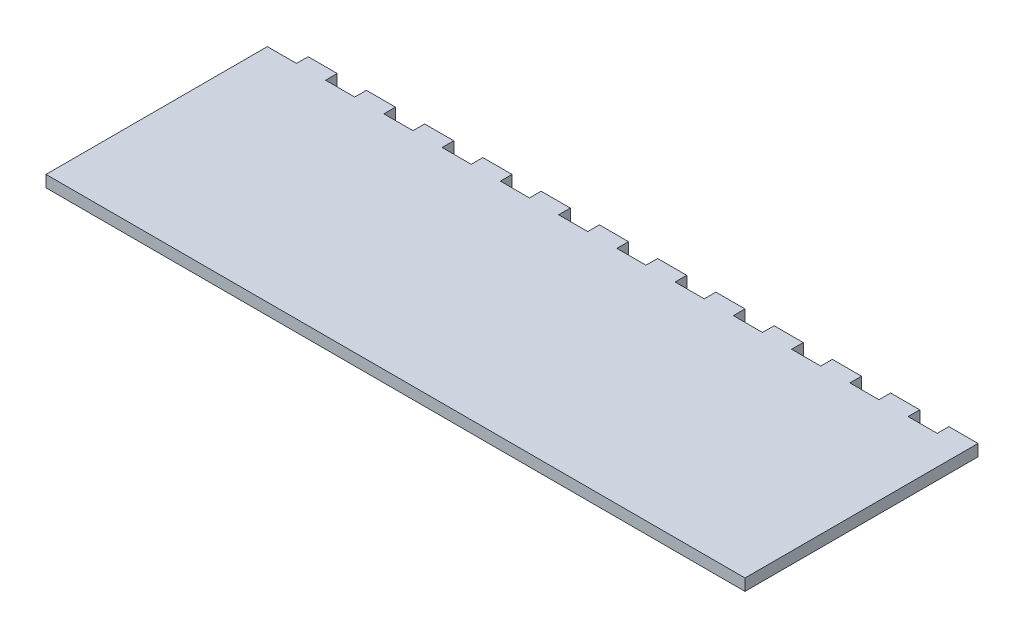
SolidWorks part; units mm, degrees
ref_plane "Front Plane" through (0, 0, 0) normal (0, 0, 1) x (1, 0, 0)
ref_plane "Top Plane" through (0, 0, 0) normal (0, 1, 0) x (1, 0, 0)
ref_plane "Right Plane" through (0, 0, 0) normal (1, 0, 0) x (0, 0, -1)
sketch "Sketch1" plane through (0, 0, 0) normal (0, 1, 0) x (1, 0, 0)
  line L1 (-76.2, -25.4) -> (76.2, -25.4)
  line L2 (-76.2, -25.4) -> (-76.2, 25.4)
  line L3 (-76.2, 25.4) -> (76.2, 25.4)
  line L4 (76.2, -25.4) -> (76.2, 25.4)
  line L5 (-76.2, -25.4) -> (76.2, 25.4) construction
  line L6 (-76.2, 25.4) -> (76.2, -25.4) construction
  point P0 (0, 0)
  dimension "D1" = 152.4
  dimension "D2" = 50.8
extrude "Boss-Extrude1" add sketch "Sketch1" along normal blind 2.54
sketch "Sketch2" plane through (0, 2.54, 0) normal (0, 1, 0) x (1, 0, 0)
  line L0 (-76.2, 22.86) -> (-69.85, 22.86)
  line L1 (-76.2, 25.4) -> (-76.2, -25.4) construction
  line L2 (-69.85, 22.86) -> (-69.85, 25.4)
  line L3 (76.2, 25.4) -> (-76.2, 25.4) construction
  line L4 (-69.85, 25.4) -> (-63.5, 25.4)
  line L5 (-76.2, 22.86) -> (-76.2, 25.4)
  line L6 (-63.5, 22.86) -> (-63.5, 25.4)
  line L7 (-63.5, 22.86) -> (-57.15, 22.86)
  line L8 (-57.15, 22.86) -> (-57.15, 25.4)
  line L9 (-57.15, 25.4) -> (-50.8, 25.4)
  line L10 (-50.8, 22.86) -> (-50.8, 25.4)
  line L11 (-50.8, 22.86) -> (-44.45, 22.86)
  line L12 (-44.45, 22.86) -> (-44.45, 25.4)
  line L13 (-44.45, 25.4) -> (-38.1, 25.4)
  line L14 (-38.1, 22.86) -> (-38.1, 25.4)
  line L15 (-38.1, 22.86) -> (-31.75, 22.86)
  line L16 (-31.75, 22.86) -> (-31.75, 25.4)
  line L17 (-31.75, 25.4) -> (-25.4, 25.4)
  line L18 (-25.4, 22.86) -> (-25.4, 25.4)
  line L19 (-25.4, 22.86) -> (-19.05, 22.86)
  line L20 (-19.05, 22.86) -> (-19.05, 25.4)
  line L21 (-19.05, 25.4) -> (-12.7, 25.4)
  line L22 (-12.7, 22.86) -> (-12.7, 25.4)
  line L23 (-12.7, 22.86) -> (-6.35, 22.86)
  line L24 (-6.35, 22.86) -> (-6.35, 25.4)
  line L25 (-6.35, 25.4) -> (0, 25.4)
  line L26 (0, 22.86) -> (0, 25.4)
  line L27 (0, 22.86) -> (6.35, 22.86)
  line L28 (6.35, 22.86) -> (6.35, 25.4)
  line L29 (6.35, 25.4) -> (12.7, 25.4)
  line L30 (12.7, 22.86) -> (12.7, 25.4)
  line L31 (12.7, 22.86) -> (19.05, 22.86)
  line L32 (19.05, 22.86) -> (19.05, 25.4)
  line L33 (19.05, 25.4) -> (25.4, 25.4)
  line L34 (25.4, 22.86) -> (25.4, 25.4)
  line L35 (25.4, 22.86) -> (31.75, 22.86)
  line L36 (31.75, 22.86) -> (31.75, 25.4)
  line L37 (31.75, 25.4) -> (38.1, 25.4)
  line L38 (38.1, 22.86) -> (38.1, 25.4)
  line L39 (38.1, 22.86) -> (44.45, 22.86)
  line L40 (44.45, 22.86) -> (44.45, 25.4)
  line L41 (44.45, 25.4) -> (50.8, 25.4)
  line L42 (50.8, 22.86) -> (50.8, 25.4)
  line L43 (50.8, 22.86) -> (57.15, 22.86)
  line L44 (57.15, 22.86) -> (57.15, 25.4)
  line L45 (57.15, 25.4) -> (63.5, 25.4)
  line L46 (63.5, 22.86) -> (63.5, 25.4)
  line L47 (63.5, 22.86) -> (69.85, 22.86)
  line L48 (69.85, 22.86) -> (69.85, 25.4)
  line L49 (69.85, 25.4) -> (76.2, 25.4)
  line L50 (-76.2, 25.4) -> (76.2, 25.4)
  line M5 (76.2, 25.4) -> (-76.2, 25.4)
  line M6 (-76.2, 25.4) -> (-76.2, -25.4)
  dimension "D1" = 2.54
  dimension "D2" = 6.35
  dimension "D3" = 6.35
  dimension "D4" = 12
extrude "Cut-Extrude1" cut sketch "Sketch2" against normal blind 2.54 contours L0 L2 M5 M6 | L7 L8 L6 M5 | L11 L12 L10 M5 | L15 L16 L14 M5 | L19 L20 L18 M5 | L23 L24 L22 M5 | L31 L32 L30 M5 | L27 L28 L26 M5 | L35 L36 L34 M5 | L39 L40 L38 M5 | L43 L44 L42 M5 | L47 L48 L46 M5 region at (-73.025, 2.54, -24.13) region at (66.675, 2.54, -24.13) region at (53.975, 2.54, -24.13) region at (41.275, 2.54, -24.13) region at (28.575, 2.54, -24.13) region at (15.875, 2.54, -24.13) region at (3.175, 2.54, -24.13) region at (-9.525, 2.54, -24.13) region at (-22.225, 2.54, -24.13) region at (-34.925, 2.54, -24.13) region at (-47.625, 2.54, -24.13) region at (-60.325, 2.54, -24.13)
